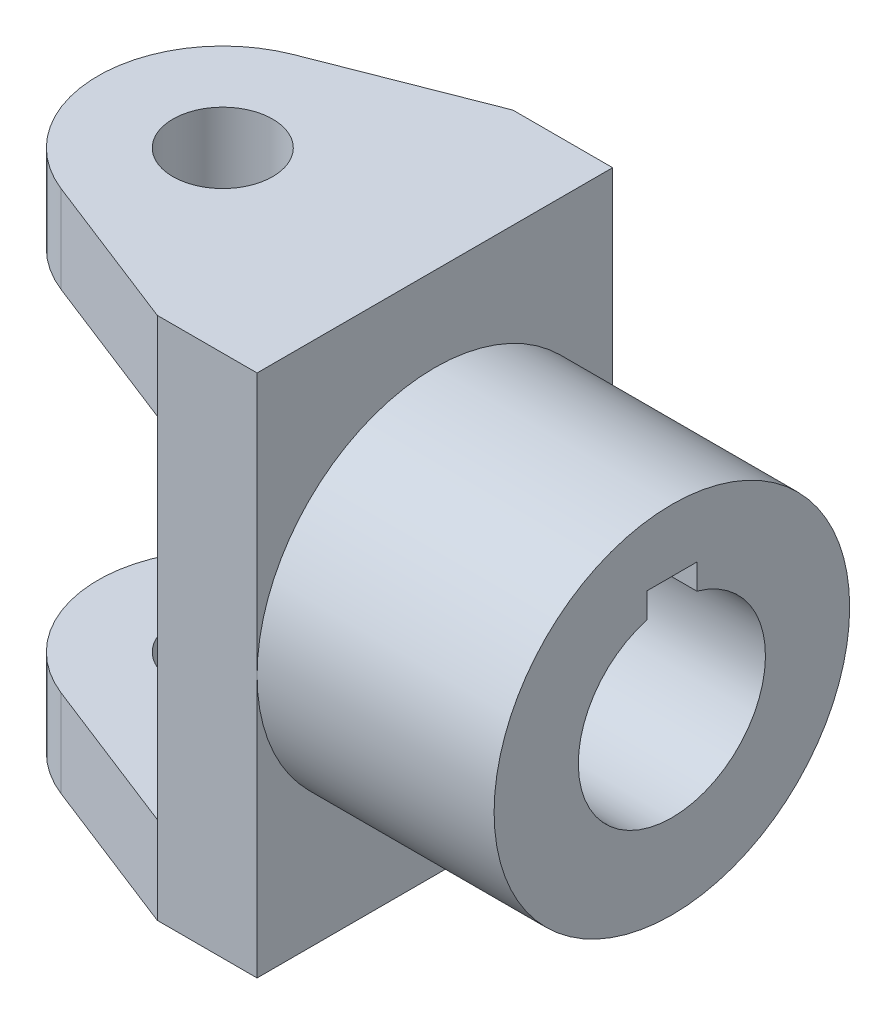
SolidWorks part; units mm, degrees
ref_plane "Front Plane" through (0, 0, 0) normal (0, 0, 1) x (1, 0, 0)
ref_plane "Top Plane" through (0, 0, 0) normal (0, 1, 0) x (1, 0, 0)
ref_plane "Right Plane" through (0, 0, 0) normal (1, 0, 0) x (0, 0, -1)
sketch "Sketch1" plane through (0, 0, 0) normal (1, 0, 0) x (0, 0, -1)
  circle A0 centre (0, 0) radius 15
  circle A1 centre (0, 0) radius 28.5
  dimension "D1" = 30
  dimension "D2" = 57
extrude "Boss-Extrude1" add sketch "Sketch1" along normal blind 38
sketch "Sketch3" plane through (0, 0, 0) normal (-1, 0, 0) x (0, 0, 1)
  line L1 (28.5, -42) -> (-28.5, -42)
  line L2 (28.5, -42) -> (28.5, 42)
  line L3 (28.5, 42) -> (-28.5, 42)
  line L4 (-28.5, -42) -> (-28.5, 42)
  line L5 (28.5, -42) -> (-28.5, 42) construction
  line L6 (28.5, 42) -> (-28.5, -42) construction
  circle A0 centre (0, 0) radius 15 construction
  circle A1 centre (0, 0) radius 15
  point P0 (0, 0)
  dimension "D1" = 57
  dimension "D2" = 84
extrude "Boss-Extrude2" add sketch "Sketch3" along normal blind 16
sketch "Sketch4" plane through (0, 42, 0) normal (0, 1, 0) x (1, 0, 0)
  line L0 (-16, 28.5) -> (-41.2751, 18.6299)
  line L1 (-41.2751, -18.6299) -> (-16, -28.5)
  line L2 (0, 0) -> (-84.0651, 0) construction
  line L4 (0, -28.5) -> (0, 28.5)
  line L5 (0, 28.5) -> (-16, 28.5)
  line L6 (-16, 28.5) -> (-16, -28.5)
  line L7 (-16, -28.5) -> (0, -28.5)
  line L8 (0, -28.5) -> (0, 28.5)
  line L9 (0, 28.5) -> (-16, 28.5)
  line L10 (-16, 28.5) -> (-16, -28.5)
  line L11 (-16, -28.5) -> (0, -28.5)
  arc A0 (-41.2751, 18.6299) -> (-41.2751, -18.6299) centre (-34, 0) ccw
  circle A1 centre (-34, 0) radius 8
  line M11 (-16, 28.5) -> (-16, -28.5)
  dimension "D2" = 20
  dimension "D3" = 18
  dimension "D4" = 16
  dimension "D1" = 0
extrude "Boss-Extrude3" add sketch "Sketch4" against normal up to surface (84 mm away) contours L2 L0 A0 A1 M11 | L10 L2 A1 A0 L1 region at (-31.6551, 42, -12.076) region at (-31.6551, 42, 12.076) up to face at (-8, -42, 0)
sketch "Sketch5" plane through (0, 0, 0) normal (0, 1, 0) x (1, 0, 0)
  line L0 (-41.2751, -18.6299) -> (-16, -28.5) construction
  line L1 (-16, -28.5) -> (0, -28.5) construction
  line L2 (0, -28.5) -> (0, 28.5) construction
  line L3 (-16, 28.5) -> (0, 28.5) construction
  line L4 (-16, 28.5) -> (-41.2751, 18.6299) construction
  line L5 (-41.2751, -18.6299) -> (-16, -28.5)
  line L6 (-16, -28.5) -> (0, -28.5)
  line L7 (0, -28.5) -> (0, 28.5)
  line L8 (-16, 28.5) -> (0, 28.5)
  line L9 (-16, 28.5) -> (-41.2751, 18.6299)
  line L10 (-16, 28.5) -> (-16, -28.5)
  arc A0 (-41.2751, 18.6299) -> (-41.2751, -18.6299) centre (-34, 0) ccw construction
  arc A1 (-41.2751, 18.6299) -> (-41.2751, -18.6299) centre (-34, 0) ccw
extrude "Cut-Extrude1" cut sketch "Sketch5" against normal mid plane 56 contours L9 A1 L5 L10 region at (-31.9623, 0, 0)
sketch "Sketch7" plane through (38, 0, 0) normal (1, 0, 0) x (0, 0, -1)
  line L1 (-4, 18.5) -> (4, 18.5)
  line L2 (-4, 18.5) -> (-4, 11.5)
  line L3 (-4, 11.5) -> (4, 11.5)
  line L4 (4, 18.5) -> (4, 11.5)
  line L5 (-4, 18.5) -> (4, 11.5) construction
  line L6 (-4, 11.5) -> (4, 18.5) construction
  circle A0 centre (0, 0) radius 15 construction
  point P0 (0, 15)
  dimension "D1" = 8
  dimension "D2" = 18.5
extrude "Cut-Extrude2" cut sketch "Sketch7" against normal through all
